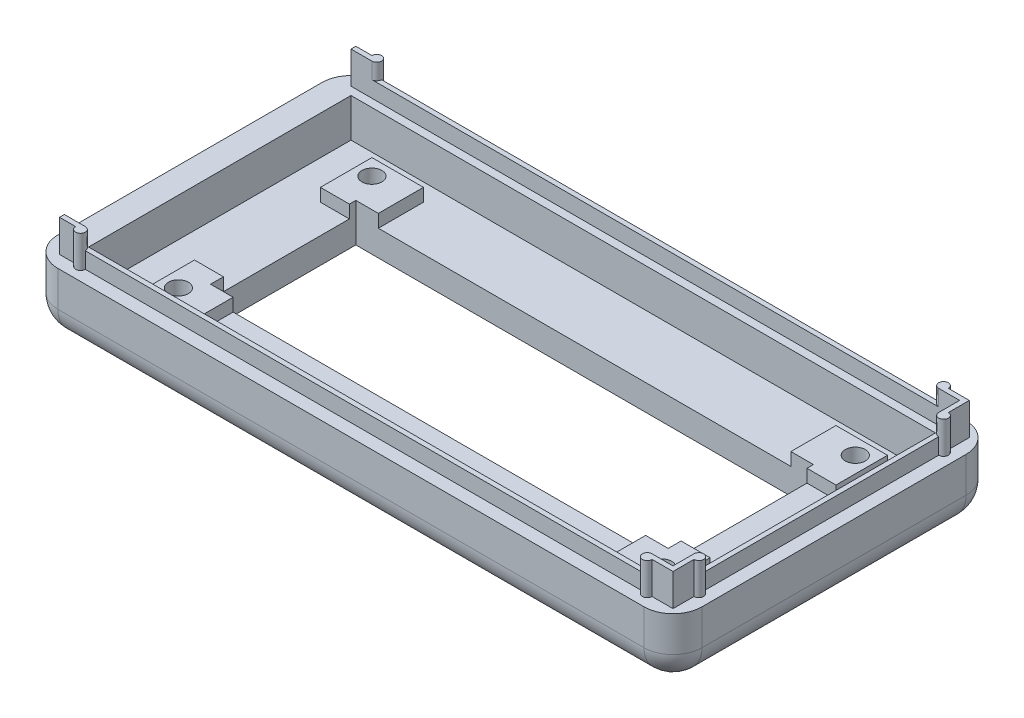
SolidWorks part; units mm, degrees
ref_plane "Спереди" through (0, 0, 0) normal (0, 0, 1) x (1, 0, 0)
ref_plane "Сверху" through (0, 0, 0) normal (0, 1, 0) x (1, 0, 0)
ref_plane "Справа" through (0, 0, 0) normal (1, 0, 0) x (0, 0, -1)
sketch "Эскиз1" plane through (0, 0, 0) normal (0, 1, 0) x (1, 0, 0)
  line L1 (0, 0) -> (100, 0)
  line L2 (0, 0) -> (0, -50)
  line L3 (0, -50) -> (100, -50)
  line L4 (100, 0) -> (100, -50)
  dimension "D1" = 50
  dimension "D2" = 100
extrude "Бобышка-Вытянуть1" add sketch "Эскиз1" along normal blind 10
shell "Оболочка1" thickness 4 removed face at (50, 10, 25)
fillet "Скругление1" radius 4.5 8 edges at (50, 0, 50) (100, 0, 25) (50, 0, 0) (0, 0, 25) (100, 5, 0) (100, 5, 50) (0, 5, 0) (0, 5, 50)
sketch "Эскиз2" plane through (0, 0, 0) normal (0, -1, 0) x (-1, 0, 0)
  line L0 (-50, -4.5) -> (-50, -45.5) construction
  line L1 (-85.525, -13.725) -> (-14.475, -13.725)
  line L2 (-85.525, -13.725) -> (-85.525, -36.275)
  line L3 (-85.525, -36.275) -> (-14.475, -36.275)
  line L4 (-14.475, -13.725) -> (-14.475, -36.275)
  line L5 (-4.5, -4.5) -> (-95.5, -4.5) construction
  line L6 (-95.5, -45.5) -> (-4.5, -45.5) construction
  line L7 (-95.5, -25) -> (-4.5, -25) construction
  line L8 (-95.5, -4.5) -> (-95.5, -45.5) construction
  line L9 (-4.5, -45.5) -> (-4.5, -4.5) construction
  dimension "D1" = 71.05
  dimension "D2" = 22.55
  dimension "D3" = 9.225
  dimension "D4" = 9.975
extrude "Вырез-Вытянуть1" cut sketch "Эскиз2" against normal blind 4.5
sketch "Эскиз6" plane through (0, 4, 0) normal (0, 1, 0) x (1, 0, 0)
  line L0 (14.475, -13.725) -> (14.475, -14.725)
  line L1 (14.475, -13.725) -> (14.475, -36.275) construction
  line L2 (14.475, -14.725) -> (9.975, -14.725)
  line L3 (9.975, -14.725) -> (9.975, -6.725)
  line L4 (9.975, -6.725) -> (17.975, -6.725)
  line L5 (17.975, -6.725) -> (17.975, -13.725)
  line L6 (85.525, -13.725) -> (14.475, -13.725) construction
  line L7 (17.975, -13.725) -> (14.475, -13.725)
  line L8 (14.475, -36.275) -> (14.475, -34.275)
  line L9 (14.475, -34.275) -> (9.975, -34.275)
  line L10 (9.975, -34.275) -> (9.975, -41.775)
  line L11 (9.975, -41.775) -> (17.975, -41.775)
  line L12 (17.975, -41.775) -> (17.975, -36.275)
  line L13 (14.475, -36.275) -> (85.525, -36.275) construction
  line L14 (17.975, -36.275) -> (14.475, -36.275)
  line L15 (50, -13.725) -> (50, -36.275) construction
  line L16 (14.475, -25) -> (85.525, -25) construction
  line L17 (85.525, -36.275) -> (85.525, -13.725) construction
  line L18 (90.025, -41.775) -> (82.025, -41.775)
  line L19 (82.025, -41.775) -> (82.025, -36.275)
  line L20 (82.025, -36.275) -> (85.525, -36.275)
  line L21 (85.525, -36.275) -> (85.525, -34.275)
  line L22 (85.525, -34.275) -> (90.025, -34.275)
  line L23 (90.025, -34.275) -> (90.025, -41.775)
  line L24 (82.025, -6.725) -> (82.025, -13.725)
  line L25 (82.025, -13.725) -> (85.525, -13.725)
  line L26 (85.525, -13.725) -> (85.525, -14.725)
  line L27 (85.525, -14.725) -> (90.025, -14.725)
  line L28 (90.025, -14.725) -> (90.025, -6.725)
  line L29 (90.025, -6.725) -> (82.025, -6.725)
  dimension "D1" = 8
  dimension "D2" = 8
  dimension "D3" = 4.5
  dimension "D4" = 4.5
  dimension "D5" = 35.05
  dimension "D6" = 8
  dimension "D7" = 2
  dimension "D8" = 7
extrude "Бобышка-Вытянуть3" add sketch "Эскиз6" along normal blind 2
sketch "Эскиз7" plane through (0, 6, 0) normal (0, 1, 0) x (1, 0, 0)
  line L0 (17.975, -6.725) -> (9.975, -6.725) construction
  line L1 (9.975, -6.725) -> (9.975, -14.725) construction
  line L2 (50, -13.725) -> (50, -36.275) construction
  line L3 (82.025, -13.725) -> (17.975, -13.725) construction
  line L4 (17.975, -36.275) -> (82.025, -36.275) construction
  line L5 (14.475, -24.5) -> (85.525, -24.5) construction
  line L6 (14.475, -14.725) -> (14.475, -34.275) construction
  line L7 (85.525, -34.275) -> (85.525, -14.725) construction
  line L8 (9.975, -34.275) -> (9.975, -41.775) construction
  line L9 (9.975, -41.775) -> (17.975, -41.775) construction
  circle A0 centre (12.475, -9.225) radius 1.55
  circle A1 centre (87.525, -9.225) radius 1.55
  circle A2 centre (12.475, -39.275) radius 1.55
  circle A3 centre (87.525, -39.275) radius 1.55
  dimension "D1" = 3.1
  dimension "D4" = 3.1
  dimension "D2" = 2.5
  dimension "D3" = 2.5
  dimension "D5" = 2.5
  dimension "D6" = 2.5
extrude "Вырез-Вытянуть2" cut sketch "Эскиз7" against normal blind 4
sketch "Эскиз8" plane through (0, 10, 0) normal (0, 1, 0) x (1, 0, 0)
  line L0 (96, -4) -> (4, -4) construction
  line L1 (2, -5.25) -> (2, -2)
  line L2 (4, -4) -> (4, -46) construction
  line L3 (50, -4) -> (50, -46) construction
  line L4 (96, -4) -> (4, -4) construction
  line L5 (4, -46) -> (96, -46) construction
  line L6 (4, -25) -> (96, -25) construction
  line L7 (4, -4) -> (4, -46) construction
  line L8 (96, -46) -> (96, -4) construction
  line L9 (2, -2) -> (5.25, -2)
  line L10 (2.75, -6) -> (2.75, -2.75)
  line L11 (2.75, -2.75) -> (6, -2.75)
  line L12 (97.25, -6) -> (97.25, -2.75)
  line L13 (97.25, -2.75) -> (94, -2.75)
  line L14 (98, -2) -> (94.75, -2)
  line L15 (98, -5.25) -> (98, -2)
  line L16 (98, -44.75) -> (98, -48)
  line L17 (98, -48) -> (94.75, -48)
  line L18 (97.25, -47.25) -> (94, -47.25)
  line L19 (97.25, -44) -> (97.25, -47.25)
  line L20 (2.75, -47.25) -> (6, -47.25)
  line L21 (2.75, -44) -> (2.75, -47.25)
  line L22 (2, -48) -> (5.25, -48)
  line L23 (2, -44.75) -> (2, -48)
  line L24 (2, -6.75) -> (2, -43.25)
  line L25 (2.75, -44) -> (2.75, -6)
  line L26 (6.75, -2) -> (93.25, -2)
  line L27 (94, -2.75) -> (6, -2.75)
  line L28 (97.25, -44) -> (97.25, -6)
  line L29 (98, -6.75) -> (98, -43.25)
  line L30 (94, -47.25) -> (6, -47.25)
  line L31 (6.75, -48) -> (93.25, -48)
  line L32 (2.75, -2.75) -> (2.75, -2)
  line L33 (2.75, -47.25) -> (2.75, -48)
  circle A0 centre (2, -6) radius 0.75
  circle A1 centre (6, -2) radius 0.75
  circle A2 centre (94, -2) radius 0.75
  circle A3 centre (98, -6) radius 0.75
  circle A4 centre (98, -44) radius 0.75
  circle A5 centre (94, -48) radius 0.75
  circle A6 centre (6, -48) radius 0.75
  circle A7 centre (2, -44) radius 0.75
  point P64 (0, 0)
  dimension "D1" = 1.5
  dimension "D4" = 1.5
  dimension "D2" = 2
  dimension "D3" = 2
  dimension "D5" = 2
  dimension "D6" = 2
extrude "Бобышка-Вытянуть5" add sketch "Эскиз8" along normal blind 5 contours A6 | A1 | A2 | L12 A3 L15 L14 A2 L13 | A3 | A4 | A5 L17 L16 A4 L19 L18 | A5 | L22 A6 L20 L33 | A1 L9 L32 L11 region at (4.0857, 10, 2.3875) region at (6, 10, 2) region at (4.0857, 10, 47.6125) region at (94.5703, 10, 2.5703) region at (94, 10, 2) region at (6, 10, 48) region at (95.625, 10, 47.3066) region at (94, 10, 48) region at (98, 10, 6) region at (98, 10, 44)
extrude "Бобышка-Вытянуть6" add sketch "Эскиз8<4>" along normal blind 2.5 contours L27 A2 L26 A1 | A4 L29 A3 L28 | L30 A6 L31 A5 region at (50, 10, 2.3758) region at (50, 10, 47.6242) region at (97.6232, 10, 25)
sketch "Эскиз8<4>" plane through (0, 10, 0) normal (0, 1, 0) x (1, 0, 0) same geometry as "Эскиз8"
